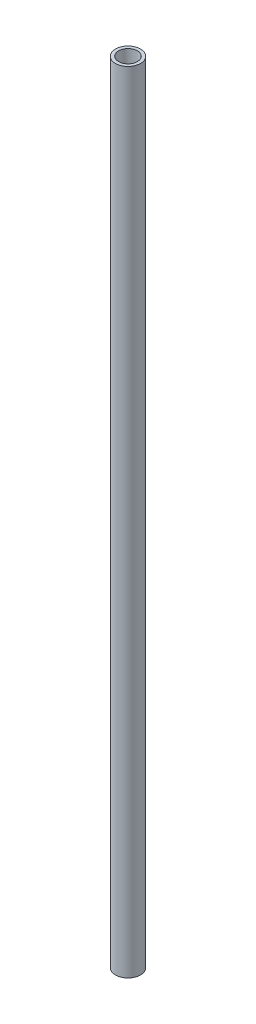
SolidWorks part; units mm, degrees
ref_plane "Front Plane" through (0, 0, 0) normal (0, 0, 1) x (1, 0, 0)
ref_plane "Top Plane" through (0, 0, 0) normal (0, 1, 0) x (1, 0, 0)
ref_plane "Right Plane" through (0, 0, 0) normal (1, 0, 0) x (0, 0, -1)
sketch "Sketch1" plane through (0, 0, 0) normal (0, 1, 0) x (1, 0, 0)
  circle A0 centre (0, 0) radius 6.35
  circle A1 centre (0, 0) radius 4.7625
  dimension "D1" = 12.7
  dimension "D2" = 9.525
extrude "Boss-Extrude1" add sketch "Sketch1" along normal blind 400.304
